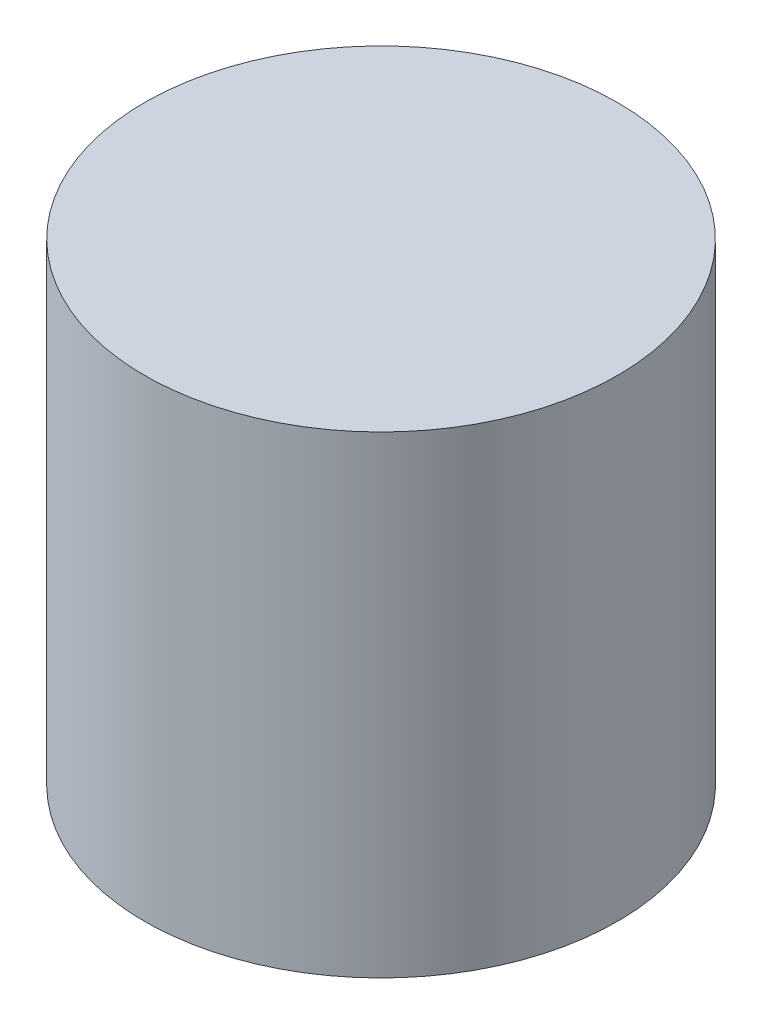
SolidWorks part; units mm, degrees
ref_plane "Front Plane" through (0, 0, 0) normal (0, 0, 1) x (1, 0, 0)
ref_plane "Top Plane" through (0, 0, 0) normal (0, 1, 0) x (1, 0, 0)
ref_plane "Right Plane" through (0, 0, 0) normal (1, 0, 0) x (0, 0, -1)
sketch "Sketch1" plane through (0, 0, 0) normal (0, 0, 1) x (1, 0, 0)
  line L0 (0, 0) -> (0, 12.7) construction
  line L1 (0, 12.7) -> (6.35, 12.7)
  line L2 (6.35, 12.7) -> (6.35, 0)
  line L3 (6.35, 0) -> (0, 0)
  line L4 (0, 0) -> (0, 12.7)
  dimension "D1" = 12.7
  dimension "D2" = 12.7
revolve "Revolve1" add sketch "Sketch1" angle 360 about L0
